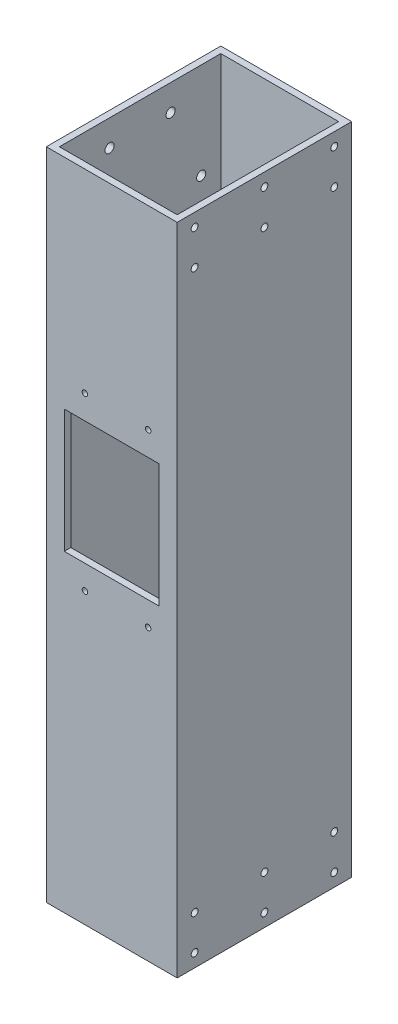
SolidWorks part; units mm, degrees
other "drill guide"
other "gp1_link"
material "6061-T6 (SS)"
ref_plane "Front Plane" through (0, 0, 0) normal (0, 0, 1) x (1, 0, 0)
ref_plane "Top Plane" through (0, 0, 0) normal (0, 1, 0) x (1, 0, 0)
ref_plane "Right Plane" through (0, 0, 0) normal (1, 0, 0) x (0, 0, -1)
sketch "Sketch1" plane through (0, 0, 0) normal (0, 1, 0) x (1, 0, 0)
  line L0 (3, 3) -> (3, 77)
  line L1 (0, 0) -> (60, 0)
  line L2 (0, 0) -> (0, 80)
  line L3 (0, 80) -> (60, 80)
  line L4 (60, 0) -> (60, 80)
  line L5 (3, 77) -> (57, 77)
  line L6 (57, 3) -> (57, 77)
  line L7 (3, 3) -> (57, 3)
  dimension "D1" = 80
  dimension "D2" = 60
  dimension "D3" = 3
extrude "Boss-Extrude1" add sketch "Sketch1" along normal blind 300
sketch "Sketch2" plane through (0, 0, 0) normal (0, 0, 1) x (1, 0, 0)
  line L0 (30, 300) -> (30, 200) construction
  line L1 (8.25, 200) -> (51.75, 200)
  line L2 (8.25, 200) -> (8.25, 143.5)
  line L3 (8.25, 143.5) -> (51.75, 143.5)
  line L4 (51.75, 200) -> (51.75, 143.5)
  line L5 (0, 300) -> (60, 300) construction
  dimension "D1" = 43.5
  dimension "D2" = 100
  dimension "D3" = 56.5
extrude "Cut-Extrude1" cut sketch "Sketch2" against normal up to next
sketch "Sketch3" plane through (0, 0, 0) normal (0, 0, 1) x (1, 0, 0)
  line L3 (15.4832, 200) -> (8.25, 200) construction
  line L4 (60, 300) -> (60, 0) construction
  line L7 (46.7, 132.5) -> (17.7, 132.5) construction
  line L9 (17.7, 211) -> (46.7, 211) construction
  line L14 (46.7, 132.5) -> (46.7, 211) construction
  line L16 (46.7, 171.75) -> (51.75, 171.75) construction
  line L17 (51.75, 143.5) -> (51.75, 200) construction
  point P0 (17.7, 211)
  point P11 (46.7, 211)
  point P12 (46.7, 132.5)
  point P13 (17.7, 132.5)
  dimension "D1" = 13.3
  dimension "D2" = 29
  dimension "D6" = 78.5
  dimension "D3" = 2
  dimension "D4" = 2
hole_wizard "Tap Drill for M3 Tap1" positions "Sketch3" profile "Sketch5" hole size "M3" standard "DIN" end condition up to next
sketch "Sketch5" plane through (17.7, 211, 0) normal (1, 0, 0) x (0, -1, 0)
  line L0 (0, 0) -> (0, 3)
  line L1 (0, 3) -> (1.25, 3)
  line L2 (1.25, 3) -> (1.25, 0)
  line L5 (1.25, 0) -> (0, 0)
  line L11 (0, -6.35) -> (0, 107.95) construction
  dimension "Thru Hole Dia." = 2.5
  dimension "Thru Hole Depth" = 3
sketch "Sketch8" plane through (0, 0, 0) normal (-1, 0, 0) x (0, 0, 1)
  line L0 (-80, 0) -> (0, 0) construction
  point P0 (-8, 6)
  point P8 (-40, 6)
  point P9 (-72, 6)
  point P10 (-40, 22)
  point P11 (-72, 22)
  point P12 (-8, 22)
  dimension "D3" = 6
  dimension "D1" = 3
  dimension "D2" = 2
hole_wizard "Tap Drill for M3 Helicoil2" positions "Sketch8" profile "Sketch7" hole size "M3x0.5" standard "DIN" end condition through all
sketch "Sketch7" plane through (0, 6, -8) normal (0, 1, 0) x (0, 0, 1)
  line L0 (0, 0) -> (0, 60)
  line L1 (0, 60) -> (1.575, 60)
  line L2 (1.575, 60) -> (1.575, 0)
  line L5 (1.575, 0) -> (0, 0)
  line L11 (0, -6.35) -> (0, 107.95) construction
  dimension "Thru Hole Dia." = 3.15
  dimension "Thru Hole Depth" = 60
sketch "Sketch11" plane through (60, 0, 0) normal (1, 0, 0) x (0, 0, -1)
  line L3 (40, 300) -> (40, 248.3318) construction
  line L4 (0, 300) -> (80, 300) construction
  point P45 (8, 294)
  point P50 (40, 294)
  point P51 (72, 294)
  point P52 (40, 278)
  point P53 (72, 278)
  point P54 (8, 278)
  dimension "D1" = 3
  dimension "D3" = 6
  dimension "D2" = 2
hole_wizard "Tap Drill for M3 Helicoil2" positions "Sketch11" profile "Sketch10" hole size "M3x0.5" standard "DIN" end condition up to next
sketch "Sketch10" plane through (60, 294, -8) normal (0, 1, 0) x (0, 0, -1)
  line L0 (0, 0) -> (0, 3)
  line L1 (0, 3) -> (1.575, 3)
  line L2 (1.575, 3) -> (1.575, 0)
  line L5 (1.575, 0) -> (0, 0)
  line L11 (0, -6.35) -> (0, 107.95) construction
  dimension "Thru Hole Dia." = 3.15
  dimension "Thru Hole Depth" = 3
sketch "Sketch14" plane through (0, 0, 0) normal (-1, 0, 0) x (0, 0, 1)
  point P0 (-68, 256)
  point P3 (-12, 256)
  point P6 (-26, 288)
  point P9 (-54, 288)
hole_wizard "Tap Drill for M5 Tap1" positions "Sketch14" profile "Sketch13" hole size "M5" standard "DIN" end condition up to next
sketch "Sketch13" plane through (0, 256, -68) normal (0, 1, 0) x (0, 0, 1)
  line L0 (0, 0) -> (0, 3)
  line L1 (0, 3) -> (2.1, 3)
  line L2 (2.1, 3) -> (2.1, 0)
  line L5 (2.1, 0) -> (0, 0)
  line L11 (0, -6.35) -> (0, 107.95) construction
  dimension "Thru Hole Dia." = 4.2
  dimension "Thru Hole Depth" = 3
sketch "Sketch15" plane through (0, 0, 0) normal (-1, 0, 0) x (0, 0, 1)
  line L0 (-80, 244) -> (-84, 244)
  line L1 (-80, 300) -> (-80, 0) construction
  line L2 (-84, 244) -> (-84, 304)
  line L3 (-84, 304) -> (4, 304)
  line L4 (4, 304) -> (4, 244)
  line L5 (4, 244) -> (0, 244)
  line L6 (0, 300) -> (0, 0) construction
  line L7 (0, 244) -> (0, 300)
  line L8 (0, 300) -> (-80, 300)
  line L9 (-80, 300) -> (0, 300) construction
  line L10 (-80, 300) -> (-80, 244)
  dimension "D1" = 4
  dimension "D2" = 4
  dimension "D3" = 60
extrude "Boss-Extrude2" add sketch "Sketch15" against normal blind 6 separate body
sketch "Sketch16" plane through (0, 0, 0) normal (-1, 0, 0) x (0, 0, 1)
  line L0 (-40, 304) -> (-40, 296) construction
  line L1 (-84, 304) -> (4, 304)
  line L2 (-84, 304) -> (-84, 244)
  line L3 (-84, 244) -> (4, 244)
  line L4 (4, 304) -> (4, 244)
  line L5 (-77.5, 282) -> (-2.5, 282)
  line L6 (-77.5, 282) -> (-77.5, 262)
  line L7 (-77.5, 262) -> (-2.5, 262)
  line L8 (-2.5, 282) -> (-2.5, 262)
  line L9 (-47.5, 282) -> (-32.5, 282)
  line L10 (-47.5, 282) -> (-47.5, 296)
  line L11 (-47.5, 296) -> (-32.5, 296)
  line L12 (-32.5, 282) -> (-32.5, 296)
  line L13 (-40, 296) -> (-40, 262) construction
  line L14 (-40, 262) -> (-40, 252) construction
  line L15 (-60, 262) -> (-20, 262)
  line L16 (-60, 262) -> (-60, 252)
  line L17 (-60, 252) -> (-20, 252)
  line L18 (-20, 262) -> (-20, 252)
  circle A0 centre (-54, 288) radius 2.9
  circle A1 centre (-26, 288) radius 2.9
  circle A2 centre (-12, 256) radius 2.9
  circle A3 centre (-68, 256) radius 2.9
  point P18 (-40, 304)
  line M22 (-80, 244) -> (-80, 300)
  line M23 (-80, 300) -> (0, 300)
  line M24 (0, 300) -> (0, 244)
  line M25 (0, 244) -> (4, 244)
  line M26 (4, 244) -> (4, 304)
  line M27 (4, 304) -> (-84, 304)
  line M28 (-84, 304) -> (-84, 244)
  line M29 (-84, 244) -> (-80, 244)
  dimension "D6" = 5.8
  dimension "D7" = 40
  dimension "D1" = 75
  dimension "D2" = 15
  dimension "D3" = 20
  dimension "D4" = 8
  dimension "D5" = 14
  dimension "D8" = 10
extrude "Boss-Extrude3" add sketch "Sketch16" along normal blind 6 contours M29 M22 M23 M24 M25 M26 M27 M28 | L3 A3 A2 A1 A0 L7 L18 L17 L16 L6 L5 L10 L11 L12 L8 M22 M24 M23 region at (0, 302.9349, -40) region at (0, 272, -79.0235)
fillet "Fillet1" radius 2 12 edges at (-3, 262, -2.5) (-3, 282, -2.5) (-3, 282, -32.5) (-3, 296, -47.5) (-3, 282, -47.5) (-3, 282, -77.5) (-3, 262, -77.5) (-3, 262, -60) (-3, 252, -60) (-3, 252, -20) (-3, 262, -20) (-3, 296, -32.5)
delete or keep bodies "Body-Delete/Keep 1" type delete bodies bodies 109
